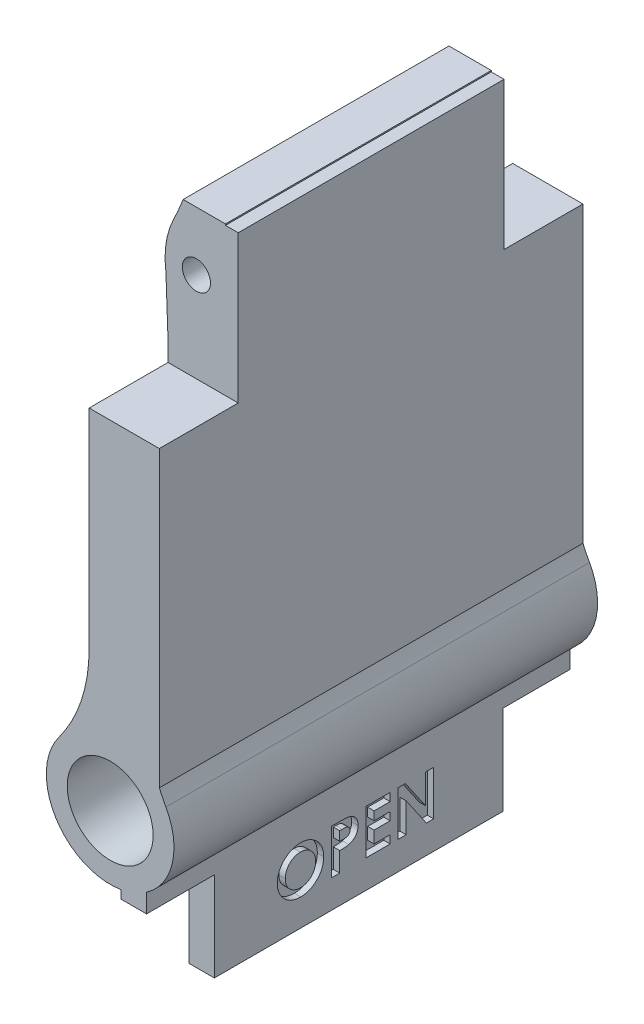
SolidWorks part; units mm, degrees
ref_plane "Front Plane" through (0, 0, 0) normal (0, 0, 1) x (1, 0, 0)
ref_plane "Top Plane" through (0, 0, 0) normal (0, 1, 0) x (1, 0, 0)
ref_plane "Right Plane" through (0, 0, 0) normal (1, 0, 0) x (0, 0, -1)
sketch "Sketch1" plane through (0, 0, 0) normal (1, 0, 0) x (0, 0, -1)
  line L1 (-12.1285, 31.1423) -> (22.1715, 31.1423)
  line L2 (-12.1285, 31.1423) -> (-12.1285, -14.3677)
  line L3 (-12.1285, -14.3677) -> (22.1715, -14.3677)
  line L4 (22.1715, 31.1423) -> (22.1715, -14.3677)
  dimension "D1" = 34.3
  dimension "D2" = 45.51
extrude "Boss-Extrude1" add sketch "Sketch1" along normal blind 2
sketch "Sketch2" plane through (2, 0, 0) normal (1, 0, 0) x (0, 0, -1)
  line L1 (-13.1789, 32.5446) -> (-5.132, 32.5446)
  line L2 (-13.1789, 32.5446) -> (-13.1789, 18.5154)
  line L3 (-11.6124, 18.5154) -> (-5.132, 18.5154)
  line L4 (-5.132, 32.5446) -> (-5.132, 18.5154)
  line L6 (-13.1789, 18.5154) -> (-13.1789, -15.2384)
  line L7 (-13.1789, -15.2384) -> (-11.6124, -15.2384)
  line L8 (-11.6124, 18.5154) -> (-11.6124, -13.5576)
  line L9 (-11.6124, -15.2384) -> (22.7351, -15.2384)
  line L11 (-11.6124, -13.5576) -> (22.7351, -13.5576)
  line L12 (22.7351, -15.2384) -> (22.7351, -13.5576)
extrude "Cut-Extrude1" cut sketch "Sketch2" against normal blind 2
ref_plane "Plane1" through (0, 0, -5.2796) normal (0, 0, 1) x (1, 0, 0)
mirror "Mirror1" about plane through (0, 0, -5.2796) normal (0, 0, 1) of "Cut-Extrude1"
sketch "Sketch3" plane through (0, 0, -15.6911) normal (0, 0, -1) x (-1, 0, 0)
  line L0 (1.3154, 30.165) -> (0, 30.165)
  line L2 (0, 20.0801) -> (0, 30.165)
  line L3 (2.4021, 23.4206) -> (1.3154, 20.0801)
  line L4 (1.3154, 20.0801) -> (0, 20.0801)
  arc A0 (0.8697, 31.4648) -> (2.0428, 28.4929) centre (20, 37.2986) ccw construction
  arc A1 (0, 20.0801) -> (2.0428, 28.4929) centre (-4.0326, 25.5137) ccw construction
  arc A2 (1.3154, 30.165) -> (2.0428, 28.4929) centre (20, 37.2986) ccw
  arc A3 (2.4021, 23.4206) -> (2.0428, 28.4929) centre (-4.0326, 25.5137) ccw
extrude "Boss-Extrude2" add sketch "Sketch3" against normal up to surface (20.8231 mm away) up to face at (1, 24.8288, 5.132)
sketch "Sketch4" plane through (0, 0, -15.6911) normal (0, 0, -1) x (-1, 0, 0)
  circle A3 centre (0.2762, 25.5597) radius 1.1043
extrude "Cut-Extrude2" cut sketch "Sketch4" against normal through all
sketch "Sketch5" plane through (0, 0, -22.1715) normal (0, 0, -1) x (-1, 0, 0)
  circle A2 centre (0.8513, -7.9797) radius 5
  dimension "D1" = 10
extrude "Boss-Extrude3" add sketch "Sketch5" against normal up to surface (33.7839 mm away) up to face at (1, 2.4789, 11.6124)
sketch "Sketch6" plane through (0, 0, -22.1715) normal (0, 0, -1) x (-1, 0, 0)
  circle A0 centre (0.8513, -7.9797) radius 3.365
  dimension "D1" = 6.73
extrude "Cut-Extrude3" cut sketch "Sketch6" against normal blind 13.462
mirror "Mirror2" about plane through (0, 0, -5.2796) normal (0, 0, 1) of "Cut-Extrude3"
sketch "Sketch7" plane through (0, 0, 0) normal (-1, 0, 0) x (0, 0, 1)
  line L8 (-22.1715, 18.5154) -> (-22.1715, -3.0527)
  line L9 (-22.1715, -3.0527) -> (11.6124, -3.0527)
  line L10 (11.6124, -3.0527) -> (11.6124, 18.5154)
  line L12 (11.6124, -3.0527) -> (11.6124, 18.5154)
  line L13 (5.132, 20.0801) -> (-15.6911, 20.0801)
  line L15 (11.6124, 18.5154) -> (5.132, 18.5154)
  line L16 (-22.1715, 18.5154) -> (-22.1715, -3.0527)
  line L17 (-22.1715, -3.0527) -> (11.6124, -3.0527)
  line L24 (5.132, 20.0801) -> (-15.6911, 20.0801)
  line L25 (11.6124, 18.5154) -> (5.132, 18.5154)
  line L26 (5.132, 18.5154) -> (5.132, 20.0801)
  line L27 (5.132, 18.5154) -> (5.132, 20.0801)
  line L28 (-15.6911, 20.0801) -> (-15.6911, 18.5154)
  line L29 (-15.6911, 20.0801) -> (-15.6911, 18.5154)
  line L30 (-15.6911, 18.5154) -> (-22.1715, 18.5154)
  line L31 (-15.6911, 18.5154) -> (-22.1715, 18.5154)
  dimension "D1" = 0
extrude "Boss-Extrude4" add sketch "Sketch7" along normal blind 2.5
sketch "Sketch8" plane through (0, 0, -15.6911) normal (0, 0, -1) x (-1, 0, 0)
  line L5 (2.6638, 24.542) -> (2.5, 20.0801)
  line L6 (2.5, 20.0801) -> (1.3154, 20.0801)
  line L7 (1.3154, 20.0801) -> (2.4021, 23.4206) construction
  line L8 (2.5, 20.0801) -> (1.3154, 20.0801) construction
  line L9 (1.3154, 20.0801) -> (2.6638, 24.542)
  arc A1 (2.4021, 23.4206) -> (2.0428, 28.4929) centre (-4.0326, 25.5137) ccw construction
extrude "Boss-Extrude5" add sketch "Sketch8" against normal up to surface (20.8231 mm away) up to face at (-0.2762, 26.6639, 5.132)
sketch "Sketch9" plane through (0, 0, -22.1715) normal (0, 0, -1) x (-1, 0, 0)
  line L0 (2.5, -3.0527) -> (2.6443, -3.3122)
  line L1 (2.6443, -3.3122) -> (1.7026, -3.0527)
  line L2 (1.7026, -3.0527) -> (2.5, -3.0527)
  arc A0 (0, -12.9067) -> (1.7026, -3.0527) centre (0.8513, -7.9797) ccw construction
extrude "Boss-Extrude6" add sketch "Sketch9" against normal up to surface (33.7839 mm away) up to face at (-0.1645, -2.8786, 11.6124)
fillet "Fillet2" radius 12 1 edges at (-2.5, -3.0527, -5.2796)
fillet "Fillet3" radius 12 1 edges at (-2.6443, -3.3122, -5.2796)
fillet "Fillet4" radius 12 1 edges at (2, -3.8724, -5.2796)
sketch "Sketch10" plane through (0, 31.1423, 0) normal (0, 1, 0) x (1, 0, 0)
  line L4 (2, 15.6911) -> (0, 15.6911)
  line L5 (0, 15.6911) -> (0, -5.132)
  line L6 (0, -5.132) -> (2, -5.132)
  line L7 (2, -5.132) -> (2, 15.6911)
  line L8 (2, 15.6911) -> (0, 15.6911)
  line L10 (0, -5.132) -> (2, -5.132)
  line L11 (2, -5.132) -> (2, 15.6911)
  line L12 (0, 15.6911) -> (0, -5.132)
  dimension "D1" = 0
extrude "Cut-Extrude4" cut sketch "Sketch10" against normal up to surface (0.9772 mm away) up to face at (-0.6577, 30.165, -5.2796)
sketch "Sketch11" plane through (0, -13.5576, 0) normal (0, -1, 0) x (1, 0, 0)
  line L0 (2, -22.1715) -> (2, 11.6124) construction
  line L1 (2, 6.0038) -> (0, 6.0038)
  line L2 (2, 6.0038) -> (2, -16.6236)
  line L3 (2, -16.6236) -> (0, -16.6236)
  line L4 (0, 6.0038) -> (0, -16.6236)
  line L5 (0, 6.6304) -> (0, -17.3696) construction
extrude "Boss-Extrude7" add sketch "Sketch11" along normal blind 7
sketch "Sketch12" plane through (0, 0, 11.6124) normal (0, 0, 1) x (1, 0, 0)
  line L6 (-2.5, 18.5154) -> (-2.5, 2.1551)
  line L8 (0, -13.5576) -> (2, -13.5576)
  line L9 (2, -13.5576) -> (2, -12.087)
  line L10 (2, 0.2931) -> (2, 18.5154)
  line L11 (2, 18.5154) -> (-2.5, 18.5154)
  line L14 (0, -13.5576) -> (2, -13.5576)
  line L15 (2, -13.5576) -> (2, -12.087)
  line L16 (2, 0.2931) -> (2, 18.5154)
  line L17 (2, 18.5154) -> (-2.5, 18.5154)
  line L18 (-2.5, 18.5154) -> (-2.5, 2.1551)
  line L20 (0, -12.9067) -> (0, -13.5576)
  line L21 (0, -12.9067) -> (0, -13.5576)
  arc A3 (-4.8656, -4.9989) -> (-2.5, 2.1551) centre (-14.5, 2.1551) ccw
  arc A6 (2, -12.087) -> (3.5167, -5.5465) centre (-0.8513, -7.9797) ccw
  arc A7 (2, 0.2931) -> (3.5167, -5.5465) centre (14, 0.2931) ccw
  arc A10 (2, -12.087) -> (3.5167, -5.5465) centre (-0.8513, -7.9797) ccw
  arc A11 (2, 0.2931) -> (3.5167, -5.5465) centre (14, 0.2931) ccw
  arc A12 (-4.8656, -4.9989) -> (-2.5, 2.1551) centre (-14.5, 2.1551) ccw
  arc A13 (-4.8656, -4.9989) -> (0, -12.9067) centre (-0.8513, -7.9797) ccw
  arc A14 (-4.8656, -4.9989) -> (0, -12.9067) centre (-0.8513, -7.9797) ccw
  dimension "D1" = 0
extrude "Cut-Extrude5" cut sketch "Sketch12" against normal blind 0.3
mirror "Mirror3" about plane through (0, 0, -5.2796) normal (0, 0, 1) of "Cut-Extrude5"
sketch "Sketch14" plane through (0, 0, 11.3124) normal (0, 0, 1) x (1, 0, 0)
  line L0 (2, 18.5154) -> (2, 30.165) construction
  line L1 (2, 30.0654) -> (3, 30.0654)
  line L2 (2, 30.0654) -> (2, -5.4128)
  line L3 (2, -5.4128) -> (3, -5.4128)
  line L4 (3, 30.0654) -> (3, -5.4128)
  dimension "D1" = 1
extrude "Boss-Extrude9" add sketch "Sketch14" against normal up to surface (33.1839 mm away) contours L2 L3 L4 L1 up to face at (0.0438, -2.5402, -21.8715)
sketch "Sketch17" plane through (0, 30.0654, 0) normal (0, 1, 0) x (1, 0, 0)
  line L1 (2, 15.6911) -> (3, 15.6911)
  line L2 (2, 15.6911) -> (2, 21.8715)
  line L3 (2, 21.8715) -> (3, 21.8715)
  line L4 (3, 15.6911) -> (3, 21.8715)
  line L5 (2, -5.132) -> (3, -5.132)
  line L6 (2, -5.132) -> (2, -11.3124)
  line L7 (2, -11.3124) -> (3, -11.3124)
  line L8 (3, -5.132) -> (3, -11.3124)
extrude "Cut-Extrude6" cut sketch "Sketch17" against normal up to surface (11.55 mm away) up to face at (-0.25, 18.5154, 8.2222)
sketch "Sketch18" plane through (2, 0, 0) normal (1, 0, 0) x (0, 0, -1)
  text T0 "<b>OPEN</b>"
extrude "Cut-Extrude7" cut sketch "Sketch18" against normal blind 0.5
